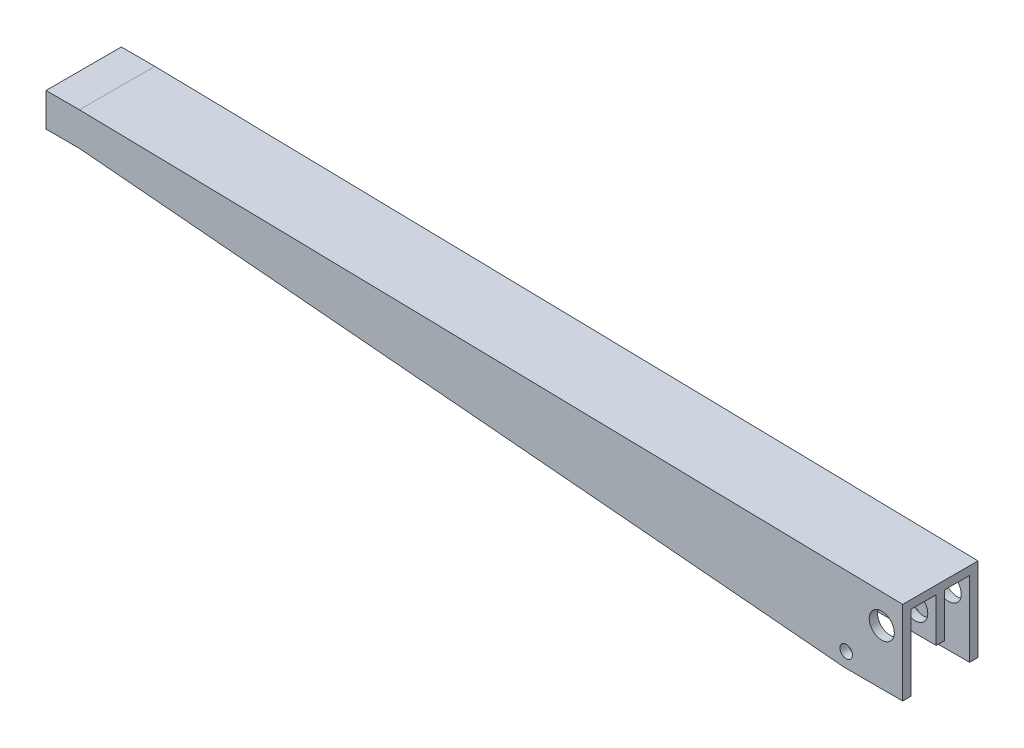
SolidWorks part; units mm, degrees
material "AISI 1045 Steel, cold drawn"
ref_plane "Front Plane" through (0, 0, 0) normal (0, 0, 1) x (1, 0, 0)
ref_plane "Top Plane" through (0, 0, 0) normal (0, 1, 0) x (1, 0, 0)
ref_plane "Right Plane" through (0, 0, 0) normal (1, 0, 0) x (0, 0, -1)
sketch "Sketch1" plane through (0, 0, 0) normal (0, 0, 1) x (1, 0, 0)
  line L0 (-2600, 304.8) -> (-2498.4, 304.8)
  line L1 (-2600, 304.8) -> (-2600, 203.2)
  line L2 (-2600, 203.2) -> (-2498.4, 203.2)
  line L4 (-177.8, 0) -> (0, 0)
  line L5 (0, 0) -> (0, 254)
  line L6 (0, 254) -> (-2498.4, 304.8)
  line L7 (-2498.4, 203.2) -> (-177.8, 0)
  dimension "D1" = 101.6
  dimension "D2" = 101.6
  dimension "D3" = 2600
  dimension "D4" = 177.8
  dimension "D6" = 203.2
  dimension "D7" = 254
extrude "Boss-Extrude1" add sketch "Sketch1" against normal blind 25.4
ref_plane "Plane1" through (0, 0, 177.8) normal (0, 0, 1) x (1, 0, 0)
sketch "Sketch2" plane through (0, 0, 177.8) normal (0, 0, 1) x (1, 0, 0)
  line L8 (-2498.4, 203.2) -> (-177.8, 0)
  line L10 (-177.8, 0) -> (0, 0)
  line L11 (0, 0) -> (0, 254)
  line L12 (0, 254) -> (-2498.4, 304.8)
  line L13 (-2498.4, 304.8) -> (-2600, 304.8)
  line L14 (-2600, 304.8) -> (-2600, 203.2)
  line L15 (-2600, 203.2) -> (-2498.4, 203.2)
  line L16 (-2498.4, 203.2) -> (-177.8, 0)
  line L18 (-177.8, 0) -> (0, 0)
  line L19 (0, 0) -> (0, 254)
  line L20 (0, 254) -> (-2498.4, 304.8)
  line L21 (-2498.4, 304.8) -> (-2600, 304.8)
  line L22 (-2600, 304.8) -> (-2600, 203.2)
  line L23 (-2600, 203.2) -> (-2498.4, 203.2)
  dimension "D1" = 0
extrude "Boss-Extrude2" add sketch "Sketch2" along normal blind 25.4 separate body
sketch "Sketch3" plane through (0, 0, 203.2) normal (0, 0, 1) x (1, 0, 0)
  line L6 (-2600, 279.4) -> (-2600, 304.8)
  line L7 (-2600, 304.8) -> (-2498.4, 304.8)
  line L8 (-2498.4, 304.8) -> (0, 254)
  line L9 (-25.4, 0) -> (-25.4, 229.1112)
  line L10 (-25.4, 229.1112) -> (-2498.6582, 279.4)
  line L11 (-2498.6582, 279.4) -> (-2600, 279.4)
  line L12 (-25.4, 229.1112) -> (0, 228.5947)
  line L13 (-25.4, 229.1112) -> (-2498.6582, 279.4)
  line L14 (-2498.6582, 279.4) -> (-2600, 279.4)
  line L15 (0, 0) -> (0, 254) construction
  line L16 (0, 228.5947) -> (0, 254)
  dimension "D1" = 25.4
extrude "Boss-Extrude3" add sketch "Sketch3" against normal up to surface (203.2 mm away) up to face at (-1482.0857, 181.4286, 0)
ref_plane "Plane2" through (0, 0, 88.9) normal (0, 0, 1) x (1, 0, 0)
sketch "Sketch6" plane through (0, 0, 88.9) normal (0, 0, 1) x (1, 0, 0)
  line L8 (-2498.4, 203.2) -> (-177.8, 0)
  line L10 (-177.8, 0) -> (0, 0)
  line L11 (0, 0) -> (0, 254)
  line L12 (0, 254) -> (-2498.4, 304.8)
  line L13 (-2498.4, 304.8) -> (-2600, 304.8)
  line L14 (-2600, 304.8) -> (-2600, 203.2)
  line L15 (-2600, 203.2) -> (-2498.4, 203.2)
  line L16 (-2498.4, 203.2) -> (-177.8, 0)
  line L18 (-177.8, 0) -> (0, 0)
  line L19 (0, 0) -> (0, 254)
  line L20 (0, 254) -> (-2498.4, 304.8)
  line L21 (-2498.4, 304.8) -> (-2600, 304.8)
  line L22 (-2600, 304.8) -> (-2600, 203.2)
  line L23 (-2600, 203.2) -> (-2498.4, 203.2)
  dimension "D1" = 0
extrude "Boss-Extrude4" add sketch "Sketch6" along normal blind 12.7 and the other way blind 12.7
sketch "Sketch5" plane through (0, 0, 203.2) normal (0, 0, 1) x (1, 0, 0)
  line L1 (0, 228.5947) -> (-2498.6582, 279.4) construction
  line L2 (-177.8, 0) -> (0, 0) construction
  line L3 (0, 0) -> (0, 254) construction
  circle A0 centre (-63.5, 166.3806) radius 38.1
  circle A1 centre (-171.45, 44.45) radius 19.05
  point P2 (-25.4, 166.3806)
  point P5 (-63.5, 204.4806)
  point P9 (-171.45, 25.4)
  point P10 (-190.5, 44.45)
  point P13 (-101.6, 166.3806)
  point P21 (-152.4, 44.45)
  dimension "D1" = 25.4
  dimension "D3" = 76.2
  dimension "D6" = 38.1
  dimension "D2" = 25.4
  dimension "D4" = 25.4
  dimension "D5" = 50.8
extrude "Cut-Extrude1" cut sketch "Sketch5" against normal through all
sketch "Sketch7" plane through (0, 0, 101.6) normal (0, 0, 1) x (1, 0, 0)
  line L0 (-1265.5813, 95.25) -> (0, 95.25)
  line L1 (0, 95.25) -> (0, 0)
  line L2 (0, 0) -> (-177.8, 0)
  line L3 (-177.8, 0) -> (0, 0) construction
  line L4 (0, 0) -> (0, 228.5947) construction
  line L5 (-2498.4, 203.2) -> (-177.8, 0) construction
  line L6 (-1265.5813, 95.25) -> (-177.8, 0)
  dimension "D1" = 95.25
extrude "Cut-Extrude2" cut sketch "Sketch7" against normal up to surface (25.4 mm away) up to face at (-152.4, 44.45, 76.2)
sketch "Sketch8" plane through (0, 304.8, 0) normal (0, 1, 0) x (1, 0, 0)
  line L0 (-2600, -88.9) -> (-2498.4, -88.9) construction
  line L1 (-2600, 25.4) -> (-2600, -203.2) construction
  line L2 (-2498.4, 25.4) -> (-2498.4, -203.2) construction
  line L3 (-2549.2, 25.4) -> (-2549.2, -203.2) construction
  line L4 (-2498.4, 25.4) -> (-2600, 25.4) construction
  line L5 (-2498.4, -203.2) -> (-2600, -203.2) construction
  circle A0 centre (-2549.2, -88.9) radius 25.4
  dimension "D1" = 50.8
